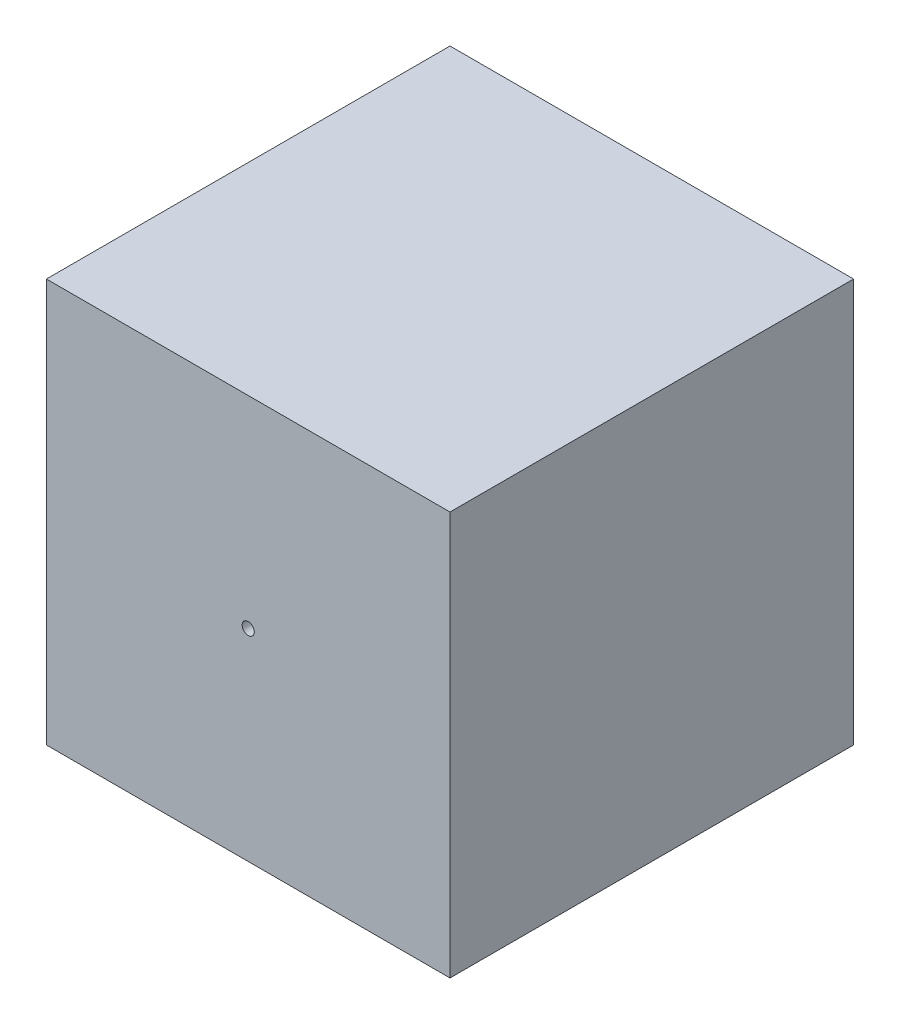
SolidWorks part; units mm, degrees
ref_plane "Alzado" through (0, 0, 0) normal (0, 0, 1) x (1, 0, 0)
ref_plane "Planta" through (0, 0, 0) normal (0, 1, 0) x (1, 0, 0)
ref_plane "Vista lateral" through (0, 0, 0) normal (1, 0, 0) x (0, 0, -1)
sketch "Croquis1" plane through (0, 0, 0) normal (0, 0, 1) x (1, 0, 0)
  line L1 (-50, -50) -> (50, -50)
  line L2 (-50, -50) -> (-50, 50)
  line L3 (-50, 50) -> (50, 50)
  line L4 (50, -50) -> (50, 50)
  line L5 (-50, -50) -> (50, 50) construction
  line L6 (-50, 50) -> (50, -50) construction
  point P0 (0, 0)
  dimension "D1" = 100
  dimension "D2" = 100
extrude "Saliente-Extruir1" add sketch "Croquis1" along normal blind 100
sketch "Croquis2" plane through (0, 0, 100) normal (0, 0, 1) x (1, 0, 0)
  circle A0 centre (0, 0) radius 1.5
  dimension "D1" = 3
extrude "Cortar-Extruir1" cut sketch "Croquis2" against normal through all
